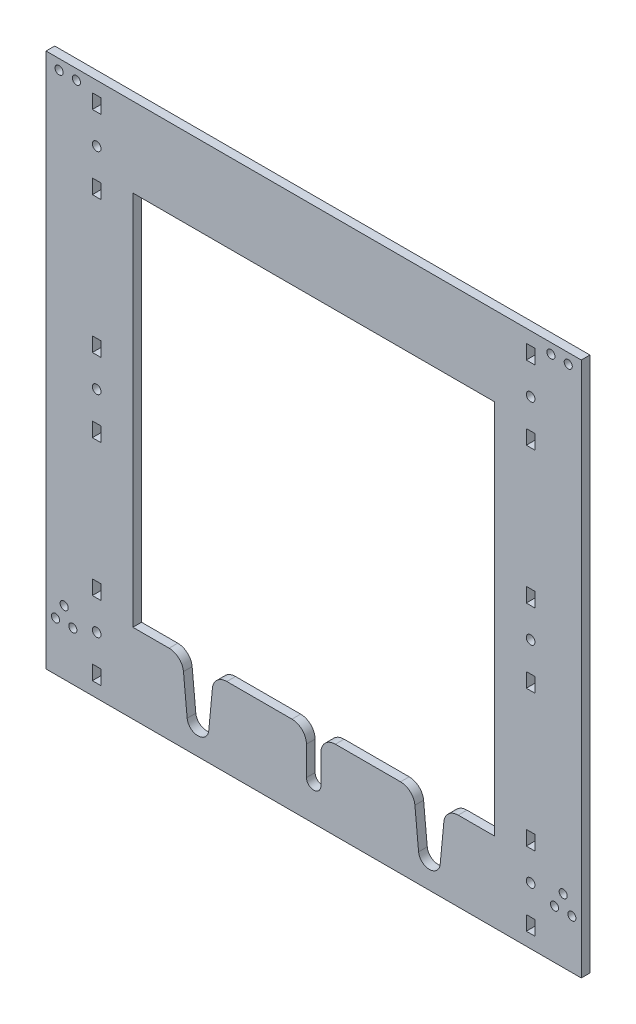
SolidWorks part; units mm, degrees
ref_plane "Front Plane" through (0, 0, 0) normal (0, 0, 1) x (1, 0, 0)
ref_plane "Top Plane" through (0, 0, 0) normal (0, 1, 0) x (1, 0, 0)
ref_plane "Right Plane" through (0, 0, 0) normal (1, 0, 0) x (0, 0, -1)
sketch "Sketch1" plane through (0, 0, 0) normal (0, 0, 1) x (1, 0, 0)
  line L0 (185, 185) -> (-185, -185) construction
  line L1 (-185, 185) -> (185, 185)
  line L2 (-185, 185) -> (-185, -185)
  line L3 (-185, -185) -> (185, -185)
  line L4 (185, 185) -> (185, -185)
  line L5 (-125, 130) -> (125, -130) construction
  line L6 (-125, 130) -> (125, 130)
  line L7 (-125, 130) -> (-125, -130)
  line L8 (-125, -130) -> (-99.9551, -130)
  line L9 (125, 130) -> (125, -130)
  line L10 (-150, 185) -> (-150, 176) construction
  line L11 (0, 185) -> (0, -185) construction
  line L12 (-150, 166) -> (-150, 145.5) construction
  line L13 (-153, 176) -> (-147, 176)
  line L14 (-153, 176) -> (-153, 166)
  line L15 (-153, 166) -> (-147, 166)
  line L16 (-147, 176) -> (-147, 166)
  line L17 (-150, 145.5) -> (-150, 125) construction
  line L18 (-150, 115) -> (-150, 30.5) construction
  line L19 (-153, 125) -> (-147, 125)
  line L20 (-153, 125) -> (-153, 115)
  line L21 (-153, 115) -> (-147, 115)
  line L22 (-147, 125) -> (-147, 115)
  line L23 (-150, 0) -> (-150, 20.5) construction
  line L24 (-153, 30.5) -> (-147, 30.5)
  line L25 (-153, 30.5) -> (-153, 20.5)
  line L26 (-153, 20.5) -> (-147, 20.5)
  line L27 (-147, 30.5) -> (-147, 20.5)
  line L28 (-150, 0) -> (-150, -20.5) construction
  line L29 (-150, -30.5) -> (-150, -115) construction
  line L30 (-153, -20.5) -> (-147, -20.5)
  line L31 (-153, -20.5) -> (-153, -30.5)
  line L32 (-153, -30.5) -> (-147, -30.5)
  line L33 (-147, -20.5) -> (-147, -30.5)
  line L34 (-150, -125) -> (-150, -145.5) construction
  line L35 (-153, -115) -> (-147, -115)
  line L36 (-153, -115) -> (-153, -125)
  line L37 (-153, -125) -> (-147, -125)
  line L38 (-147, -115) -> (-147, -125)
  line L39 (-150, -145.5) -> (-150, -166) construction
  line L40 (-150, -176) -> (-150, -185) construction
  line L41 (-153, -166) -> (-147, -166)
  line L42 (-153, -166) -> (-153, -176)
  line L43 (-153, -176) -> (-147, -176)
  line L44 (-147, -166) -> (-147, -176)
  line L45 (153, -176) -> (147, -176)
  line L46 (147, -166) -> (147, -176)
  line L47 (153, -166) -> (147, -166)
  line L48 (153, -166) -> (153, -176)
  line L49 (147, -115) -> (147, -125)
  line L50 (153, -125) -> (147, -125)
  line L51 (153, -115) -> (153, -125)
  line L52 (153, -115) -> (147, -115)
  line L53 (153, -30.5) -> (147, -30.5)
  line L54 (147, -20.5) -> (147, -30.5)
  line L55 (153, -20.5) -> (153, -30.5)
  line L56 (153, -20.5) -> (147, -20.5)
  line L57 (153, 20.5) -> (147, 20.5)
  line L58 (147, 30.5) -> (147, 20.5)
  line L59 (153, 30.5) -> (147, 30.5)
  line L60 (153, 30.5) -> (153, 20.5)
  line L61 (153, 115) -> (147, 115)
  line L62 (147, 125) -> (147, 115)
  line L63 (153, 125) -> (153, 115)
  line L64 (153, 125) -> (147, 125)
  line L65 (147, 176) -> (147, 166)
  line L66 (153, 166) -> (147, 166)
  line L67 (153, 176) -> (147, 176)
  line L68 (153, 176) -> (153, 166)
  line L69 (-80, -165) -> (-80, -185) construction
  line L70 (-90.8606, -130) -> (-69.1394, -130) construction
  line L71 (-90, -139.0538) -> (-87.4663, -165.7097)
  line L72 (-72.5337, -165.7097) -> (-70, -139.0538)
  line L73 (-80, -165) -> (-80, -130) construction
  line L74 (-60.0449, -130) -> (-15, -130)
  line L75 (-90, -139.0538) -> (-70, -139.0538) construction
  line L76 (90, -139.0538) -> (87.4663, -165.7097)
  line L77 (72.5337, -165.7097) -> (70, -139.0538)
  line L78 (99.9551, -130) -> (125, -130)
  line L79 (-178.5, -151.196) -> (-172.5, -140.8037) construction
  line L80 (5, -140) -> (5, -160)
  line L81 (-5, -140) -> (-5, -160)
  line L82 (-172.5, -140.8037) -> (-166.5, -151.196) construction
  line L83 (-166.5, -151.196) -> (-178.5, -151.196) construction
  line L84 (-176, 178) -> (-164, 178) construction
  line L85 (15, -130) -> (60.0449, -130)
  circle A0 centre (-150, 145.5) radius 3
  circle A1 centre (-150, 0) radius 3
  circle A2 centre (-150, -145.5) radius 3
  circle A3 centre (150, -145.5) radius 3
  circle A4 centre (150, 0) radius 3
  circle A5 centre (150, 145.5) radius 3
  arc A6 (-87.4663, -165.7097) -> (-72.5337, -165.7097) centre (-80, -165) ccw
  arc A7 (-99.9551, -130) -> (-90, -139.0538) centre (-99.9551, -140) cw
  arc A8 (-70, -139.0538) -> (-60.0449, -130) centre (-60.0449, -140) cw
  arc A9 (87.4663, -165.7097) -> (72.5337, -165.7097) centre (80, -165) cw
  arc A10 (70, -139.0538) -> (60.0449, -130) centre (60.0449, -140) ccw
  arc A11 (99.9551, -130) -> (90, -139.0538) centre (99.9551, -140) ccw
  arc A12 (15, -130) -> (5, -140) centre (15, -140) ccw
  arc A13 (-5, -160) -> (5, -160) centre (0, -160) ccw
  arc A14 (-5, -140) -> (-15, -130) centre (-15, -140) ccw
  circle A15 centre (-178.5, -151.196) radius 2.8
  circle A16 centre (-166.5, -151.196) radius 2.8
  circle A17 centre (-172.5, -140.8037) radius 2.8
  circle A18 centre (-176, 178) radius 2.8
  circle A19 centre (-164, 178) radius 2.8
  circle A20 centre (166.5, -151.196) radius 2.8
  circle A21 centre (172.5, -140.8037) radius 2.8
  circle A22 centre (178.5, -151.196) radius 2.8
  circle A23 centre (164, 178) radius 2.8
  circle A24 centre (176, 178) radius 2.8
  point P27 (-147, -171)
  point P58 (147, -171)
  dimension "D3" = 6
  dimension "D5" = 6
  dimension "D10" = 10
  dimension "D12" = 7.5
  dimension "D13" = 10
  dimension "D16" = 5
  dimension "D17" = 20
  dimension "D18" = 12
  dimension "D19" = 5.6
  dimension "D20" = 33.804
  dimension "D22" = 12
  dimension "D23" = 5.6
  dimension "D1" = 370
  dimension "D2" = 250
  dimension "D4" = 10
  dimension "D6" = 9
  dimension "D7" = 41
  dimension "D8" = 35
  dimension "D9" = 105
  dimension "D11" = 20
  dimension "D14" = 20
  dimension "D15" = 260
  dimension "D21" = 6.5
  dimension "D24" = 7
  dimension "D25" = 9
extrude "Boss-Extrude1" add sketch "Sketch1" along normal mid plane 6
